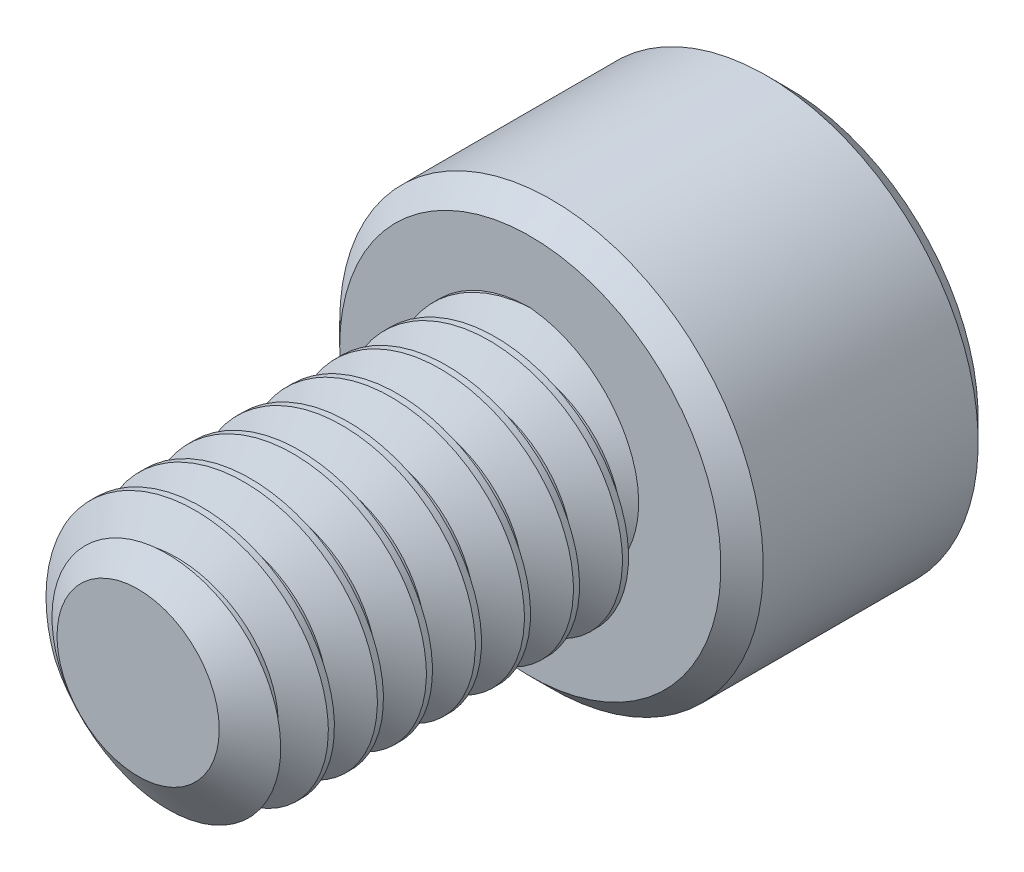
SolidWorks part; units mm, degrees
ref_plane "Front Plane" through (0, 0, 0) normal (0, 0, 1) x (1, 0, 0)
ref_plane "Top Plane" through (0, 0, 0) normal (0, 1, 0) x (1, 0, 0)
ref_plane "Right Plane" through (0, 0, 0) normal (1, 0, 0) x (0, 0, -1)
sketch "Sketch1" plane through (0, 0, 0) normal (0, 0, 1) x (1, 0, 0)
  circle A0 centre (0, 0) radius 2.0828
  dimension "OD" = 4.1656
extrude "Extrude1" add sketch "Sketch1" against normal blind 6.35
sketch "Sketch2" plane through (0, 0, 0) normal (0, 0, 1) x (1, 0, 0)
  circle A0 centre (0, 0) radius 2.0828 construction
  circle A1 centre (0, 0) radius 2.0828
curve "Helix/Spiral1" pitch 0.7937 height 7.1437 radius 2.0828 centre (0, 0, 0) axis (0, 0, -1) start towards (0, 1, 0) parameters "pitch"=0.7937
sketch "Sketch3" plane through (0, 0, 0) normal (1, 0, 0) x (0, 0, -1)
  line L0 (-0.6945, 2.0828) -> (-0.3969, 1.5672)
  line L1 (-0.3969, 1.5672) -> (-0.2977, 1.5672)
  line L2 (-0.2977, 1.5672) -> (0, 2.0828)
  line L3 (-0.6945, 2.0828) -> (0, 2.0828)
  line L4 (-0.3473, 2.0828) -> (-0.3473, 1.5672) construction
  line L5 (-0.5457, 1.825) -> (-0.1488, 1.825) construction
  line L6 (0, 2.0828) -> (0, -2.0828) construction
  dimension "D1" = 0.0992
  dimension "D2" = 0.3969
  dimension "D3" = 60
sweep "Cut-Sweep1" cut profiles "Sketch3" path "Helix/Spiral1"
sketch "Sketch4" plane through (0, 0, 0) normal (1, 0, 0) x (0, 0, -1)
  line L0 (0.5388, 2.0828) -> (0, 1.3132)
  line L1 (0, 1.3132) -> (0, 2.0828)
  line L2 (0.5388, 2.0828) -> (0, 2.0828)
  line L3 (-0.6945, 2.0828) -> (0, 2.0828) construction
  line L4 (0, 0) -> (7.0209, 0) construction
  dimension "D1" = 55
  dimension "D2" = 0.254
revolve "Cut-Revolve1" cut sketch "Sketch4" angle 360 about L4
sketch "Sketch5" plane through (0, 0, 0) normal (1, 0, 0) x (0, 0, -1)
  line L0 (6.35, -1.5805) -> (6.35, 1.4861) construction
  line L1 (6.35, 2.2098) -> (87.4327, 2.2098)
  line L2 (6.35, 2.2098) -> (6.35, 0)
  line L3 (6.35, 0) -> (87.3125, 0)
  line L4 (87.3125, 1.8796) -> (87.3125, 0)
  line L5 (87.4327, 2.2098) -> (87.3125, 1.8796)
  line L6 (0, 0) -> (9.9695, 0) construction
  point P3 (87.3125, 2.2098)
  point P10 (87.3125, 2.2098)
  dimension "D1" = 0.3302
  dimension "Thread min" = 87.3125
  dimension "D2" = 0.127
  dimension "D3" = 20
revolve "partially thread" [suppressed] add sketch "Sketch5" angle 360 about L6
sketch "Sketch6" plane through (0, 0, -6.35) normal (0, 0, -1) x (-1, 0, 0)
  circle A0 centre (0, 0) radius 3.429
  dimension "head dia" = 6.858
extrude "Extrude2" add sketch "Sketch6" along normal blind 4.1656
sketch "Sketch7" plane through (0, 0, -10.5156) normal (0, 0, -1) x (-1, 0, 0)
  line L1 (0, 2.0622) -> (-1.7859, 1.0311)
  line L2 (-1.7859, 1.0311) -> (-1.7859, -1.0311)
  line L3 (-1.7859, -1.0311) -> (0, -2.0622)
  line L4 (0, -2.0622) -> (1.7859, -1.0311)
  line L5 (1.7859, -1.0311) -> (1.7859, 1.0311)
  line L6 (1.7859, 1.0311) -> (0, 2.0622)
  circle A0 centre (0, 0) radius 1.7859 construction
  dimension "hex dia" = 3.5719
extrude "Cut-Extrude1" cut sketch "Sketch7" against normal blind 2.6789
sketch "Sketch8" plane through (0, 0, -10.5156) normal (0, 0, -1) x (-1, 0, 0)
  circle A0 centre (0, 0) radius 2.0622
extrude "Cut-Extrude2" cut sketch "Sketch8" against normal through all draft 45
chamfer "Chamfer1" distance 0.3429 angle 45 2 edges at (-3.429, 0, -10.5156) (-3.429, 0, -6.35)
sketch "Sketch9" plane through (0, 0, 0) normal (1, 0, 0) x (0, 0, -1)
  line L0 (0, 2.0828) -> (0, -2.0828) construction
  line L1 (4.3656, 2.0828) -> (4.3656, -2.0828) construction
  dimension "D1" = 4.3656
equation "\"D3@Helix/Spiral1\" = \"screw length@Extrude1\"+\"pitch@Helix/Spiral1\""
equation "\"D1@Sketch3\" = \"pitch@Helix/Spiral1\"*.125"
equation "\"D2@Sketch3\" = \"pitch@Helix/Spiral1\"*.5"
equation "\"D1@Cut-Extrude1\" = \"hex dia@Sketch7\"*.75"
equation "\"D1@Chamfer1\" = \"head dia@Sketch6\"*.05"
equation "\"D1@Sketch9\" = \"pitch@Helix/Spiral1\"*5.5"
